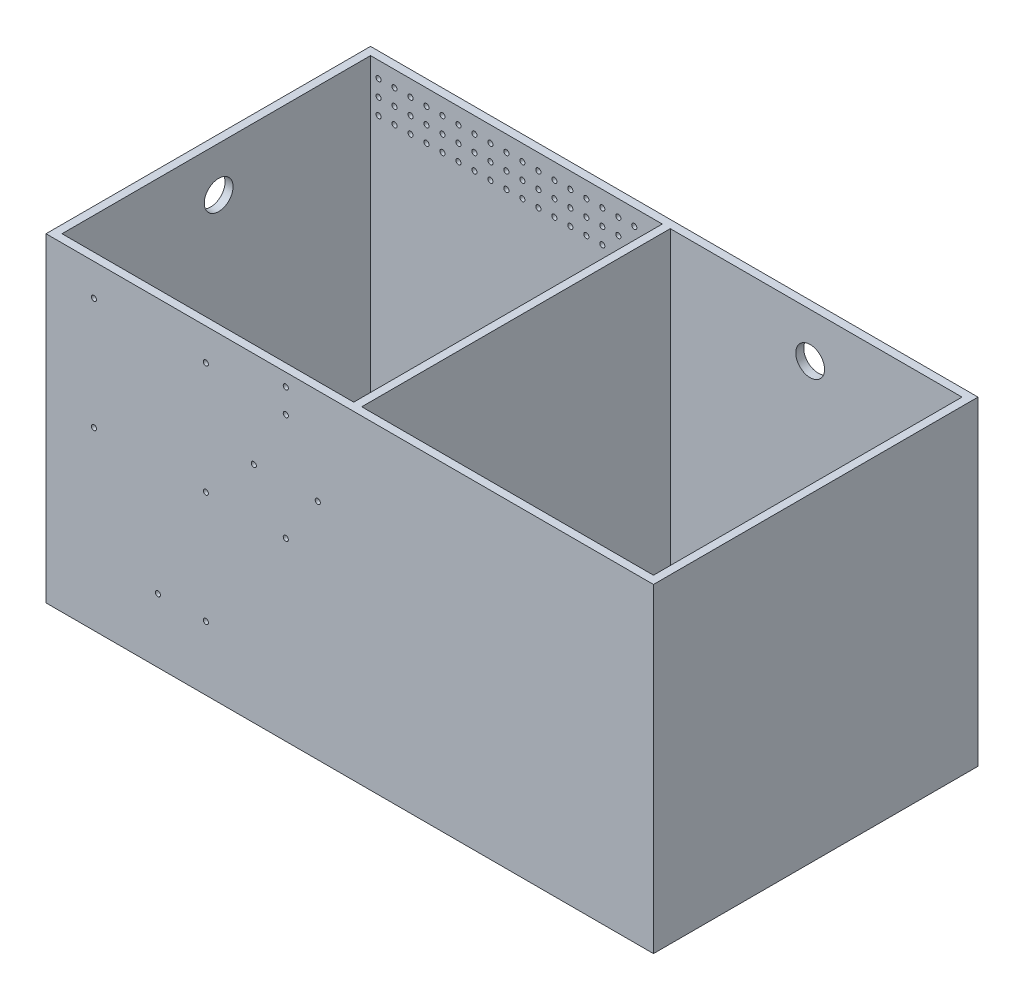
SolidWorks part; units mm, degrees
ref_plane "前视基准面" through (0, 0, 0) normal (0, 0, 1) x (1, 0, 0)
ref_plane "上视基准面" through (0, 0, 0) normal (0, 1, 0) x (1, 0, 0)
ref_plane "右视基准面" through (0, 0, 0) normal (1, 0, 0) x (0, 0, -1)
other "Configuration Table"
sketch "草图1" plane through (0, 0, 0) normal (0, 1, 0) x (1, 0, 0)
  line L0 (-190, 78.5) -> (-190, 101.5)
  line L1 (-167, 101.5) -> (167, 101.5)
  line L2 (-190, 78.5) -> (-190, -78.5)
  line L3 (-167, -101.5) -> (167, -101.5)
  line L4 (190, 78.5) -> (190, -78.5)
  line L5 (-190, 101.5) -> (190, -101.5) construction
  line L6 (-190, -101.5) -> (190, 101.5) construction
  line L7 (-190, 101.5) -> (-167, 101.5)
  line L8 (167, 101.5) -> (190, 101.5)
  line L9 (190, 101.5) -> (190, 78.5)
  line L10 (-190, -78.5) -> (-190, -101.5)
  line L11 (-190, -101.5) -> (-167, -101.5)
  line L12 (190, -78.5) -> (190, -101.5)
  line L13 (190, -101.5) -> (167, -101.5)
  point P0 (0, 0)
  dimension "D1" = 380
  dimension "D2" = 203
extrude "凸台-拉伸1" add sketch "草图1" along normal blind 200
sketch "草图3" plane through (0, 200, 0) normal (0, 1, 0) x (1, 0, 0)
  line L6 (-167, 96.5) -> (167, 96.5)
  line L8 (-185, 78.5) -> (-185, -78.5)
  line L9 (-167, -96.5) -> (167, -96.5)
  line L10 (185, 78.5) -> (185, -78.5)
  line L11 (-185, 96.5) -> (185, -96.5) construction
  line L12 (-185, -96.5) -> (185, 96.5) construction
  line L21 (-190, -101.5) -> (190, -101.5) construction
  line L22 (-190, 101.5) -> (-190, -101.5) construction
  line L23 (-185, 78.5) -> (-185, 96.5)
  line L24 (-185, 96.5) -> (-167, 96.5)
  line L25 (167, 96.5) -> (185, 96.5)
  line L26 (185, 96.5) -> (185, 78.5)
  line L27 (185, -78.5) -> (185, -96.5)
  line L28 (185, -96.5) -> (167, -96.5)
  line L29 (-185, -78.5) -> (-185, -96.5)
  line L30 (-185, -96.5) -> (-167, -96.5)
  point P0 (0, 0)
  point P1 (0, 0)
  dimension "D1" = 370
  dimension "D2" = 193
  dimension "D3" = 5
  dimension "D4" = 5
extrude "切除-拉伸1" cut sketch "草图3" against normal blind 195
sketch "草图9" plane through (190, 0, 0) normal (1, 0, 0) x (0, 0, -1)
sketch "草图11" plane through (0, 0, 101.5) normal (0, 0, 1) x (1, 0, 0)
  line L0 (-190, 200) -> (-190, 0) construction
  line L2 (-160, 180) -> (-90, 180) construction
  line L3 (-160, 180) -> (-160, 110) construction
  line L4 (-160, 110) -> (-90, 110) construction
  line L5 (-90, 180) -> (-90, 110) construction
  circle A4 centre (-160, 180) radius 1.6
  circle A5 centre (-90, 180) radius 1.6
  circle A6 centre (-160, 110) radius 1.6
  circle A7 centre (-90, 110) radius 1.6
  dimension "D2" = 70
  dimension "D3" = 70
  dimension "D10" = 30
extrude "切除-拉伸5" cut sketch "草图11" against normal up to next
sketch "草图14" plane through (0, 5, 0) normal (0, 1, 0) x (1, 0, 0)
  line L0 (-185, -96.5) -> (185, -96.5) construction
  line L3 (-2.5, 96.5) -> (2.5, 96.5)
  line L4 (-2.5, 96.5) -> (-2.5, -96.5)
  line L5 (-2.5, -96.5) -> (2.5, -96.5)
  line L6 (2.5, 96.5) -> (2.5, -96.5)
  line L7 (-2.5, 96.5) -> (2.5, -96.5) construction
  line L8 (-2.5, -96.5) -> (2.5, 96.5) construction
  point P0 (0, 0)
  dimension "D1" = 5
extrude "凸台-拉伸2" add sketch "草图14" along normal up to surface (195 mm away) up to face at (0, 200, 0)
sketch "草图15" plane through (0, 0, -101.5) normal (0, 0, -1) x (-1, 0, 0)
  line L0 (-190, 200) -> (190, 200) construction
  line L1 (-190, 0) -> (190, 0) construction
  line L2 (0, 0) -> (0, 200) construction
  line L4 (190, 200) -> (190, 0) construction
  line L6 (23.5, 75) -> (100, 75) construction
  line L7 (23.5, 75) -> (23.5, 20) construction
  line L8 (23.5, 20) -> (100, 20) construction
  line L9 (100, 75) -> (100, 20) construction
  circle A5 centre (23.5, 75) radius 2
  circle A6 centre (100, 75) radius 2
  circle A7 centre (23.5, 20) radius 2
  circle A8 centre (100, 20) radius 2
  dimension "D1" = 76.5
  dimension "D2" = 55
  dimension "D3" = 20
  dimension "D4" = 90
  dimension "D5" = 76.5
  dimension "D9" = 55
extrude "切除-拉伸8" cut sketch "草图15" against normal up to next
sketch "草图17" plane through (-190, 0, 0) normal (-1, 0, 0) x (0, 0, 1)
  line L0 (31.5, 130) -> (31.5, 78) construction
  line L2 (-101.5, 200) -> (101.5, 200) construction
  line L3 (101.5, 200) -> (101.5, 0) construction
  circle A0 centre (31.5, 130) radius 2.5
  circle A2 centre (31.5, 78) radius 2.5
  dimension "D1" = 5
  dimension "D3" = 5
  dimension "D2" = 52
  dimension "D4" = 70
  dimension "D5" = 70
extrude "切除-拉伸10" cut sketch "草图17" against normal up to next
sketch "草图19" plane through (0, 0, -101.5) normal (0, 0, -1) x (-1, 0, 0)
  line L0 (-190, 200) -> (190, 200) construction
  line L4 (-190, 200) -> (-190, 0) construction
  line L6 (91.75, 125.5) -> (91.75, 118.5) construction
  line L7 (91.75, 122) -> (190, 122) construction
  line L8 (190, 200) -> (190, 0) construction
  circle A0 centre (-90, 172) radius 9
  dimension "D3" = 18
  dimension "D1" = 28
  dimension "D2" = 100
  dimension "D4" = 98.25
extrude "切除-拉伸11" cut sketch "草图19" against normal up to next
sketch "草图20" plane through (-190, 0, 0) normal (-1, 0, 0) x (0, 0, 1)
  line L0 (-101.5, 200) -> (-101.5, 0) construction
  line L2 (-101.5, 200) -> (101.5, 200) construction
  circle A0 centre (-1.5, 172) radius 9
  dimension "D3" = 18
  dimension "D1" = 100
  dimension "D2" = 28
extrude "切除-拉伸12" cut sketch "草图20" against normal up to next
sketch "草图21" plane through (0, 0, 101.5) normal (0, 0, 1) x (1, 0, 0)
  line L0 (0, 200) -> (0, 0) construction
  line L1 (-190, 200) -> (190, 200) construction
  line L2 (-40, 110) -> (-40, 200) construction
  line L3 (-60, 140) -> (-20, 140) construction
  circle A0 centre (-40, 110) radius 1.6
  circle A1 centre (-20, 140) radius 1.6
  circle A2 centre (-60, 140) radius 1.6
  dimension "D1" = 40
  dimension "D2" = 3.2
  dimension "D5" = 3.2
  dimension "D6" = 3.2
  dimension "D3" = 90
  dimension "D4" = 20
  dimension "D7" = 40
  dimension "D8" = 30
extrude "切除-拉伸13" cut sketch "草图21" against normal up to next
sketch "草图22" plane through (0, 0, 101.5) normal (0, 0, 1) x (1, 0, 0)
  line L0 (0, 0) -> (0, 200) construction
  line L1 (-190, 200) -> (190, 200) construction
  line L4 (-40, 192) -> (-40, 177) construction
  circle A0 centre (-40, 192) radius 1.6
  circle A1 centre (-40, 177) radius 1.6
  circle A2 centre (-40, 110) radius 1.6 construction
  dimension "D1" = 3.2
  dimension "D3" = 3.2
  dimension "D2" = 8
  dimension "D4" = 15
  dimension "D5" = 40
  dimension "D6" = 67
extrude "切除-拉伸14" cut sketch "草图22" against normal up to next
sketch "草图24" plane through (0, 0, 101.5) normal (0, 0, 1) x (1, 0, 0)
  line L0 (-190, 200) -> (-190, 0) construction
  line L1 (-120, 40) -> (-90, 40) construction
  line L2 (-190, 0) -> (190, 0) construction
  circle A0 centre (-120, 40) radius 1.6
  circle A1 centre (-90, 40) radius 1.6
  dimension "D1" = 3.2
  dimension "D2" = 70
  dimension "D3" = 30
  dimension "D4" = 40
extrude "切除-拉伸15" cut sketch "草图24" against normal up to next
sketch "草图25" plane through (0, 0, -101.5) normal (0, 0, -1) x (-1, 0, 0)
  line L0 (0, 0) -> (0, 200) construction
  line L1 (-190, 200) -> (190, 200) construction
  line L2 (190, 200) -> (190, 0) construction
  circle A0 centre (180, 190) radius 1.6
  circle A1 centre (170, 190) radius 1.6
  circle A2 centre (160, 190) radius 1.6
  circle A3 centre (150, 190) radius 1.6
  circle A4 centre (140, 190) radius 1.6
  circle A5 centre (130, 190) radius 1.6
  circle A6 centre (120, 190) radius 1.6
  circle A7 centre (110, 190) radius 1.6
  circle A8 centre (100, 190) radius 1.6
  circle A9 centre (90, 190) radius 1.6
  circle A10 centre (80, 190) radius 1.6
  circle A11 centre (70, 190) radius 1.6
  circle A12 centre (60, 190) radius 1.6
  circle A13 centre (50, 190) radius 1.6
  circle A14 centre (40, 190) radius 1.6
  circle A15 centre (30, 190) radius 1.6
  circle A16 centre (20, 190) radius 1.6
  circle A17 centre (10, 190) radius 1.6
  circle A18 centre (170, 180) radius 1.6
  circle A19 centre (160, 180) radius 1.6
  circle A20 centre (150, 180) radius 1.6
  circle A21 centre (140, 180) radius 1.6
  circle A22 centre (130, 180) radius 1.6
  circle A23 centre (120, 180) radius 1.6
  circle A24 centre (110, 180) radius 1.6
  circle A25 centre (100, 180) radius 1.6
  circle A26 centre (90, 180) radius 1.6
  circle A27 centre (80, 180) radius 1.6
  circle A28 centre (70, 180) radius 1.6
  circle A29 centre (60, 180) radius 1.6
  circle A30 centre (50, 180) radius 1.6
  circle A31 centre (40, 180) radius 1.6
  circle A32 centre (30, 180) radius 1.6
  circle A33 centre (20, 180) radius 1.6
  circle A34 centre (10, 180) radius 1.6
  circle A35 centre (180, 180) radius 1.6
  circle A36 centre (80, 170) radius 1.6
  circle A37 centre (110, 170) radius 1.6
  circle A38 centre (40, 170) radius 1.6
  circle A39 centre (130, 170) radius 1.6
  circle A40 centre (70, 170) radius 1.6
  circle A41 centre (170, 170) radius 1.6
  circle A42 centre (10, 170) radius 1.6
  circle A43 centre (20, 170) radius 1.6
  circle A44 centre (120, 170) radius 1.6
  circle A45 centre (90, 170) radius 1.6
  circle A46 centre (140, 170) radius 1.6
  circle A47 centre (60, 170) radius 1.6
  circle A48 centre (100, 170) radius 1.6
  circle A49 centre (160, 170) radius 1.6
  circle A50 centre (180, 170) radius 1.6
  circle A51 centre (30, 170) radius 1.6
  circle A52 centre (150, 170) radius 1.6
  circle A53 centre (50, 170) radius 1.6
  dimension "D2" = 3.2
  dimension "D1" = 190
  dimension "D3" = 10
  dimension "D4" = 10
  dimension "D5" = 18
  dimension "D6" = 2
extrude "切除-拉伸16" cut sketch "草图25" against normal up to next (5 mm away)
